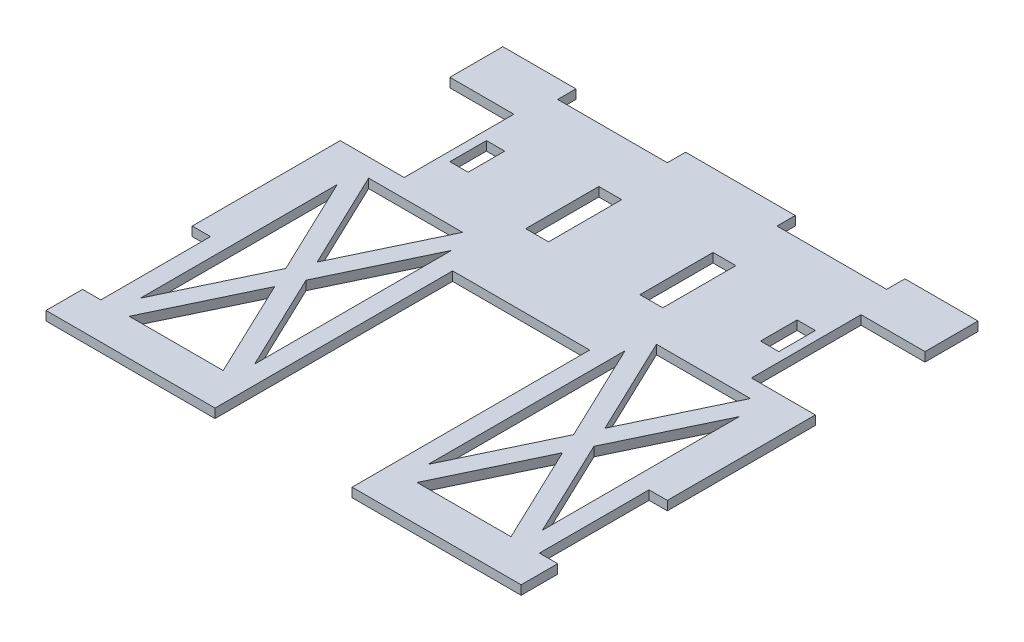
SolidWorks part; units mm, degrees
material "7050-T73510"
ref_plane "Front Plane" through (0, 0, 0) normal (0, 0, 1) x (1, 0, 0)
ref_plane "Top Plane" through (0, 0, 0) normal (0, 1, 0) x (1, 0, 0)
ref_plane "Right Plane" through (0, 0, 0) normal (1, 0, 0) x (0, 0, -1)
sketch "Sketch1" plane through (0, 0, 0) normal (0, 1, 0) x (1, 0, 0)
  line L0 (0, -55) -> (0, 55) construction
  line L1 (-165.1, -76.2) -> (165.1, -76.2)
  line L2 (-165.1, -76.2) -> (-165.1, 76.2)
  line L3 (-165.1, 76.2) -> (165.1, 76.2)
  line L4 (165.1, -76.2) -> (165.1, 76.2)
  line L5 (-165.1, -76.2) -> (165.1, 76.2) construction
  line L6 (-165.1, 76.2) -> (165.1, -76.2) construction
  line L7 (-165.1, -76.2) -> (-31.75, -76.2)
  line L8 (-165.1, -76.2) -> (-165.1, -241.3)
  line L9 (-165.1, -241.3) -> (-31.75, -241.3)
  line L10 (-31.75, -76.2) -> (-31.75, -241.3)
  line L11 (31.75, -76.2) -> (31.75, -241.3)
  line L12 (165.1, -241.3) -> (31.75, -241.3)
  line L13 (165.1, -76.2) -> (165.1, -241.3)
  line L14 (165.1, -76.2) -> (31.75, -76.2)
  line L15 (-47.625, -76.2) -> (-47.625, -241.3)
  line L16 (47.625, -76.2) -> (47.625, -241.3)
  point P0 (0, 0)
  dimension "D1" = 330.2
  dimension "D2" = 152.4
  dimension "D3" = 317.5
  dimension "D4" = 63.5
  dimension "D5" = 15.875
extrude "Boss-Extrude1" add sketch "Sketch1" along normal blind 6.35 contours L15 L1 L8 L9 | L14 L16 L12 L13 | L1 L7 L14 L4 L3 L2 region at (0, 0, 0) region at (-106.3625, 0, 158.75) region at (106.3625, 0, 158.75)
sketch "Sketch2" plane through (0, 6.35, 0) normal (0, 1, 0) x (1, 0, 0)
  line L0 (165.1, -241.3) -> (165.1, 76.2) construction
  line L1 (165.1, 39.37) -> (120.65, 39.37)
  line L2 (165.1, 39.37) -> (165.1, -36.83)
  line L3 (165.1, -36.83) -> (120.65, -36.83)
  line L4 (120.65, 39.37) -> (120.65, -36.83)
  line L5 (-165.1, 76.2) -> (165.1, 76.2) construction
  line L6 (165.1, -139.7) -> (152.4, -139.7)
  line L7 (165.1, -139.7) -> (165.1, -215.9)
  line L8 (165.1, -215.9) -> (152.4, -215.9)
  line L9 (152.4, -139.7) -> (152.4, -215.9)
  line L10 (0, -55) -> (0, 55) construction
  line L11 (-165.1, -215.9) -> (-152.4, -215.9)
  line L12 (-152.4, -139.7) -> (-152.4, -215.9)
  line L13 (-165.1, -139.7) -> (-152.4, -139.7)
  line L14 (-165.1, -139.7) -> (-165.1, -215.9)
  line L15 (-165.1, -36.83) -> (-120.65, -36.83)
  line L16 (-120.65, 39.37) -> (-120.65, -36.83)
  line L17 (-165.1, 39.37) -> (-120.65, 39.37)
  line L18 (-165.1, 39.37) -> (-165.1, -36.83)
  line L19 (-114.3, 63.5) -> (-38.1, 63.5)
  line L20 (114.3, 76.2) -> (38.1, 76.2)
  line L21 (114.3, 76.2) -> (114.3, 63.5)
  line L22 (114.3, 63.5) -> (38.1, 63.5)
  line L23 (38.1, 76.2) -> (38.1, 63.5)
  line L24 (-38.1, 76.2) -> (-38.1, 63.5)
  line L25 (-114.3, 76.2) -> (-38.1, 76.2)
  line L26 (-114.3, 76.2) -> (-114.3, 63.5)
  dimension "D1" = 44.45
  dimension "D2" = 12.7
  dimension "D3" = 76.2
  dimension "D4" = 76.2
  dimension "D5" = 36.83
  dimension "D6" = 215.9
  dimension "D7" = 76.2
  dimension "D8" = 12.7
  dimension "D9" = 76.2
extrude "Cut-Extrude1" cut sketch "Sketch2" against normal through all
sketch "Sketch3" plane through (0, 6.35, 0) normal (0, 1, 0) x (1, 0, 0)
  line L0 (-47.625, -76.2) -> (47.625, -76.2) construction
  line L1 (-47.625, -25.4) -> (-31.75, -25.4)
  line L2 (-47.625, -25.4) -> (-47.625, 25.4)
  line L3 (-47.625, 25.4) -> (-31.75, 25.4)
  line L4 (-31.75, -25.4) -> (-31.75, 25.4)
  line L5 (0, -3.4925) -> (0, 3.4925) construction
  line L6 (47.625, 25.4) -> (31.75, 25.4)
  line L7 (31.75, -25.4) -> (31.75, 25.4)
  line L8 (47.625, -25.4) -> (31.75, -25.4)
  line L9 (47.625, -25.4) -> (47.625, 25.4)
  line L10 (120.65, 39.37) -> (120.65, -36.83) construction
  line L11 (101.6, 13.97) -> (114.3, 13.97)
  line L12 (101.6, 13.97) -> (101.6, -11.43)
  line L13 (101.6, -11.43) -> (114.3, -11.43)
  line L14 (114.3, 13.97) -> (114.3, -11.43)
  line L15 (38.1, 63.5) -> (114.3, 63.5) construction
  line L16 (-101.6, -11.43) -> (-114.3, -11.43)
  line L17 (-114.3, 13.97) -> (-114.3, -11.43)
  line L18 (-101.6, 13.97) -> (-114.3, 13.97)
  line L19 (-101.6, 13.97) -> (-101.6, -11.43)
  dimension "D1" = 50.8
  dimension "D2" = 15.875
  dimension "D3" = 50.8
  dimension "D4" = 63.5
  dimension "D5" = 25.4
  dimension "D6" = 12.7
  dimension "D7" = 6.35
  dimension "D8" = 49.53
extrude "Cut-Extrude2" cut sketch "Sketch3" against normal through all
sketch "Sketch4" plane through (0, 6.35, 0) normal (0, 1, 0) x (1, 0, 0)
  line L0 (47.625, -76.2) -> (47.625, -241.3) construction
  line L1 (60.325, -215.9) -> (139.7, -215.9)
  line L2 (60.325, -215.9) -> (60.325, -49.53)
  line L3 (60.325, -49.53) -> (139.7, -49.53)
  line L4 (139.7, -215.9) -> (139.7, -49.53)
  line L5 (152.4, -139.7) -> (152.4, -215.9) construction
  line L6 (165.1, -241.3) -> (47.625, -241.3) construction
  line L7 (60.325, -215.9) -> (139.7, -49.53) construction
  line L8 (60.325, -49.53) -> (139.7, -215.9) construction
  line L9 (139.7, -201.1532) -> (67.3607, -49.53)
  line L10 (132.6643, -215.9) -> (60.325, -64.2768)
  line L11 (60.325, -201.1532) -> (132.6643, -49.53)
  line L12 (67.3607, -215.9) -> (139.7, -64.2768)
  line L13 (120.65, -36.83) -> (165.1, -36.83) construction
  line L14 (0, -3.4925) -> (0, 3.4925) construction
  line L15 (-60.325, -201.1532) -> (-132.6643, -49.53)
  line L16 (-132.6643, -215.9) -> (-60.325, -64.2768)
  line L17 (-139.7, -201.1532) -> (-67.3607, -49.53)
  line L18 (-67.3607, -215.9) -> (-139.7, -64.2768)
  line L19 (-60.325, -49.53) -> (-139.7, -49.53)
  line L20 (-139.7, -215.9) -> (-139.7, -49.53)
  line L21 (-60.325, -215.9) -> (-139.7, -215.9)
  line L22 (-60.325, -215.9) -> (-60.325, -49.53)
  point P18 (121.8313, -163.7005)
  dimension "D1" = 12.7
  dimension "D2" = 12.7
  dimension "D3" = 25.4
  dimension "D4" = 12.7
  dimension "D5" = 12.7
extrude "Cut-Extrude3" cut sketch "Sketch4" against normal through all contours L12 L9 L4 | L12 L1 L10 | L2 L11 L10 | L9 L11 L3 | L21 L18 L16 | L20 L17 L18 | L17 L19 L15 | L15 L22 L16 region at (100.0125, 6.35, 193.0873) region at (71.2089, 6.35, 132.715) region at (128.8161, 6.35, 132.715) region at (100.0125, 6.35, 72.3427) region at (-71.2089, 6.35, 132.715) region at (-100.0125, 6.35, 72.3427) region at (-100.0125, 6.35, 193.0873) region at (-128.8161, 6.35, 132.715)
